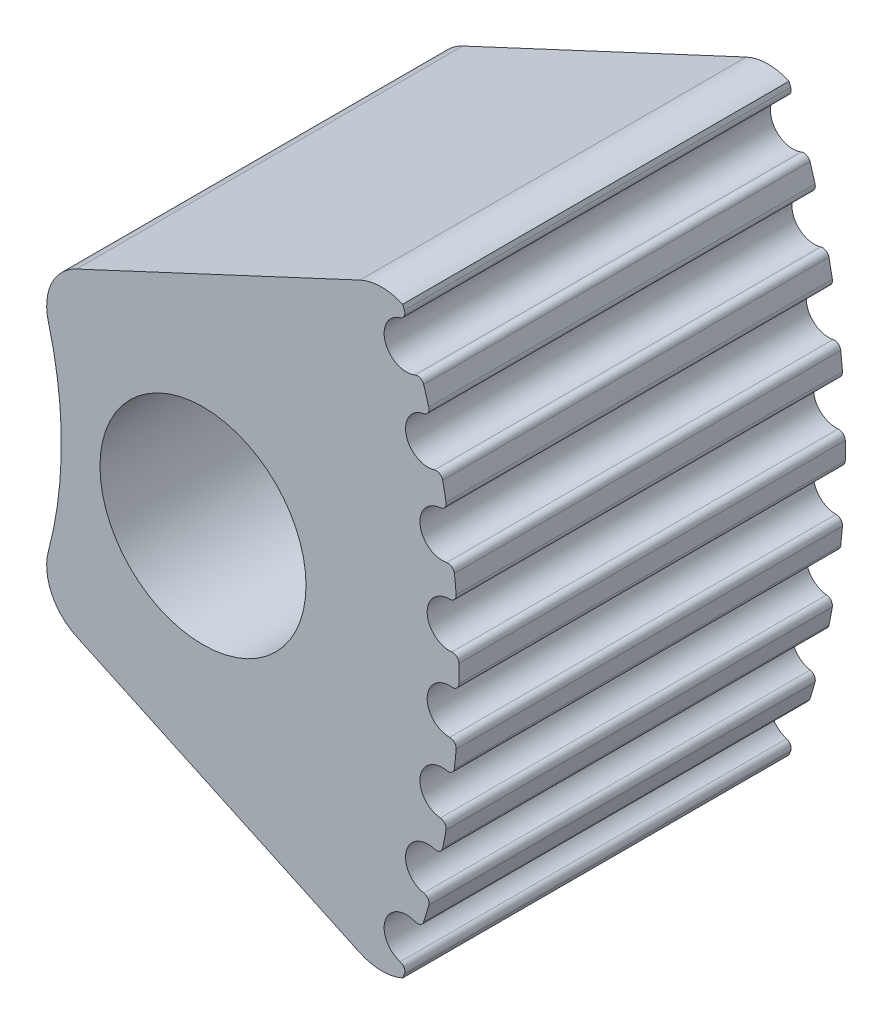
SolidWorks part; units mm, degrees
ref_plane "Front Plane" through (0, 0, 0) normal (0, 0, 1) x (1, 0, 0)
ref_plane "Top Plane" through (0, 0, 0) normal (0, 1, 0) x (1, 0, 0)
ref_plane "Right Plane" through (0, 0, 0) normal (1, 0, 0) x (0, 0, -1)
sketch "Sketch1" plane through (0, 0, 0) normal (0, 0, 1) x (1, 0, 0)
  line L0 (0, 0) -> (31.04, 0) construction
  line L1 (15.5848, 6.1776) -> (26.5969, 11.3126)
  line L2 (15.5848, -6.1776) -> (26.5969, -11.3126)
  arc A0 (14.4971, -3.8515) -> (14.4971, 3.8515) centre (0, 0) ccw
  arc A1 (29.3321, -10.1543) -> (29.3321, 10.1543) centre (0, 0) ccw
  arc A2 (26.5969, 11.3126) -> (29.3321, 10.1543) centre (27.4422, 9.5) cw
  arc A3 (15.5848, 6.1776) -> (14.4971, 3.8515) centre (16.4301, 4.365) ccw
  arc A4 (26.5969, -11.3126) -> (29.3321, -10.1543) centre (27.4422, -9.5) ccw
  arc A5 (15.5848, -6.1776) -> (14.4971, -3.8515) centre (16.4301, -4.365) cw
  dimension "D1" = 31.04
  dimension "D2" = 25
  dimension "D3" = 2
  dimension "D4" = 15
  dimension "D5" = 9.5
extrude "Corpo" add sketch "Sketch1" along normal blind 15
hole_wizard "Rebaixo - Parafuso M4" positions "Sketch5" profile "Sketch6" counterbore size "M4" standard "ANSI Metric"
sketch "Sketch5" plane through (0, 0, 15) normal (0, 0, 1) x (1, 0, 0)
  line L0 (15, 0) -> (31.04, 0) construction
  arc A0 (14.4971, -3.8515) -> (14.4971, 3.8515) centre (0, 0) ccw construction
  arc A1 (29.3321, -10.1543) -> (29.3321, 10.1543) centre (0, 0) ccw construction
  point P0 (20.5, 0)
  dimension "D1" = 5.5
sketch "Sketch6" plane through (20.5, 0, 15) normal (1, 0, 0) x (0, -1, 0)
  line L0 (0, 0) -> (0, 31.3519)
  line L1 (0, 31.3519) -> (2.25, 30)
  line L2 (2.25, 30) -> (2.25, 9)
  line L3 (2.25, 9) -> (4, 9)
  line L4 (4, 9) -> (4, 0)
  line L5 (4, 0) -> (0, 0)
  line L10 (0, 31.3519) -> (-2.25, 30) construction
  line L11 (0, -6.35) -> (0, 107.95) construction
  dimension "Hole Dia." = 4.5
  dimension "Hole Depth" = 30
  dimension "C'Bore Dia." = 8
  dimension "C'Bore Depth" = 9
  dimension "Drill Angle" = 118
sketch "Sketch7" plane through (0, 0, 15) normal (0, 0, 1) x (1, 0, 0)
  line L0 (0, 0) -> (30.44, 0) construction
  line L1 (0, 0) -> (31.0037, -1.5001) construction
  line L2 (30.44, 0) -> (31.04, 0)
  line L3 (30.2978, -2.9387) -> (30.895, -2.9966)
  arc A0 (31.04, 0) -> (30.895, -2.9966) centre (0, 0) cw
  arc A1 (30.44, 0) -> (30.4381, -0.3437) centre (0, 0) cw
  arc A2 (30.4381, -0.3437) -> (30.1628, -0.5896) centre (30.1881, -0.3409) cw
  arc A3 (30.1628, -0.5896) -> (30.0788, -2.3251) centre (30.0748, -1.4551) ccw
  arc A4 (29.3321, -10.1543) -> (29.3321, 10.1543) centre (0, 0) ccw construction
  arc A5 (30.3291, -2.5964) -> (30.0788, -2.3251) centre (30.08, -2.5751) ccw
  arc A6 (30.2978, -2.9387) -> (30.3291, -2.5964) centre (0, 0) ccw
  dimension "D1" = 0.87
  dimension "D2" = 0.25
  dimension "D4" = 1.8
  dimension "D3" = 0.6
  dimension "D5" = 2.77
extrude "Corte do Dente" cut sketch "Sketch7" against normal through all
pattern_circular "Corte dos Dentes" count 65 over 360 about axis through (0, 0, 15) along (0, 0, -1) of "Corte do Dente"
equation "\"n\"= 65'Number of Teeth"
equation "\"p\"= 3mm'Pitch"
equation "\"pd\"= \"n\" * \"p\" / pi'Pitch Diameter"
equation "\"D1@Corte dos Dentes\"=\"n\""
